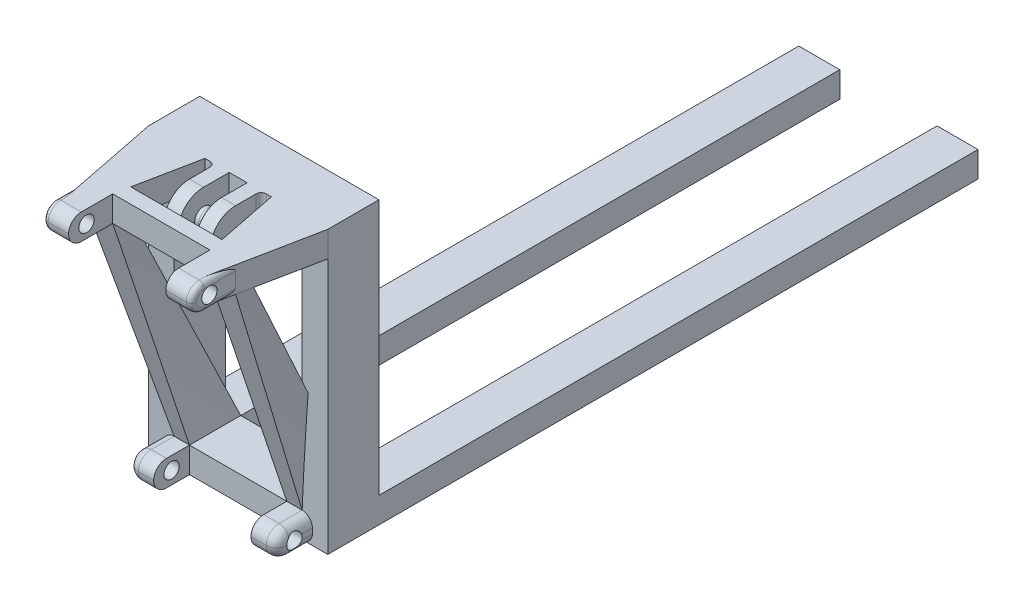
SolidWorks part; units mm, degrees
ref_plane "Front Plane" through (0, 0, 0) normal (0, 0, 1) x (1, 0, 0)
ref_plane "Top Plane" through (0, 0, 0) normal (0, 1, 0) x (1, 0, 0)
ref_plane "Right Plane" through (0, 0, 0) normal (1, 0, 0) x (0, 0, -1)
sketch "Sketch1" plane through (0, 0, 0) normal (0, 0, 1) x (1, 0, 0)
  line L1 (-17.5, -27.5) -> (17.5, -27.5)
  line L2 (-17.5, -27.5) -> (-17.5, 27.5)
  line L3 (-17.5, 27.5) -> (17.5, 27.5)
  line L4 (17.5, -27.5) -> (17.5, 27.5)
  line L5 (-17.5, -27.5) -> (17.5, 27.5) construction
  line L6 (-17.5, 27.5) -> (17.5, -27.5) construction
  point P0 (0, 0)
  dimension "D1" = 35
  dimension "D2" = 55
extrude "Boss-Extrude1" add sketch "Sketch1" along normal blind 3
sketch "Sketch2" plane through (0, 0, 3) normal (0, 0, 1) x (1, 0, 0)
  line L18 (-14.5, 27.5) -> (-9.5, 27.5)
  line L19 (-14.5, 27.5) -> (-14.5, 22.5)
  line L20 (-9.5, 27.5) -> (-9.5, 22.5)
  line L21 (-14.5, 22.5) -> (-9.5, 22.5)
  line L22 (17.5, 27.5) -> (-17.5, 27.5) construction
  line L23 (9.5, 27.5) -> (14.5, 27.5)
  line L24 (9.5, 27.5) -> (9.5, 22.5)
  line L25 (14.5, 27.5) -> (14.5, 22.5)
  line L26 (9.5, 22.5) -> (14.5, 22.5)
  line L27 (-9.5, -27.5) -> (-14.5, -27.5)
  line L28 (-9.5, -27.5) -> (-9.5, -22.5)
  line L29 (-14.5, -27.5) -> (-14.5, -22.5)
  line L30 (-9.5, -22.5) -> (-14.5, -22.5)
  line L31 (-17.5, -27.5) -> (17.5, -27.5) construction
  line L32 (9.5, -27.5) -> (14.5, -27.5)
  line L33 (9.5, -27.5) -> (9.5, -22.5)
  line L34 (14.5, -27.5) -> (14.5, -22.5)
  line L35 (9.5, -22.5) -> (14.5, -22.5)
  line L36 (-17.5, 27.5) -> (-17.5, -27.5) construction
  line L37 (17.5, -27.5) -> (17.5, 27.5) construction
  dimension "D1" = 5
  dimension "D2" = 3
  dimension "D3" = 3
  dimension "D4" = 3
  dimension "D5" = 3
  dimension "D6" = 5
extrude "Boss-Extrude2" add sketch "Sketch2" along normal blind 7
sketch "Sketch3" plane through (-14.5, 0, 0) normal (-1, 0, 0) x (0, 0, 1)
  line L0 (3, 27.5) -> (10, 22.5)
  line L1 (3, -22.5) -> (10, -27.5)
  circle A0 centre (6.5, 25) radius 1.5
  circle A1 centre (6.5, -25) radius 1.5
  dimension "D1" = 3
  dimension "D2" = 3
extrude "Cut-Extrude1" cut sketch "Sketch3" against normal up to surface (29 mm away) contours L1 A1 | L1 A1 region at (-14.5, -24.482, 6.87) region at (-14.5, -25.518, 6.13) up to face at (14.5, 25, 6.5)
fillet "Fillet1" radius 2.5 4 edges at (12, -27.5, 10) (12, -22.5, 10) (-12, -27.5, 10) (-12, -22.5, 10)
sketch "Sketch4" plane through (0, 0, 10) normal (0, 0, 1) x (1, 0, 0)
  line L1 (-9.5, 27.5) -> (-14.5, 27.5)
  line L2 (-9.5, 27.5) -> (-9.5, 22.5)
  line L3 (-9.5, 22.5) -> (-14.5, 22.5)
  line L4 (-14.5, 27.5) -> (-14.5, 22.5)
  line L5 (14.5, 27.5) -> (9.5, 27.5)
  line L6 (14.5, 27.5) -> (14.5, 22.5)
  line L7 (14.5, 22.5) -> (9.5, 22.5)
  line L8 (9.5, 27.5) -> (9.5, 22.5)
extrude "Boss-Extrude3" add sketch "Sketch4" along normal blind 16.6176
sketch "Sketch5" plane through (-14.5, 0, 0) normal (-1, 0, 0) x (0, 0, 1)
  line L0 (26.6176, 22.5) -> (3, 22.5) construction
  line L1 (26.6176, 27.5) -> (19.6176, 27.5)
  line L2 (26.6176, 27.5) -> (26.6176, 22.5)
  line L3 (26.6176, 22.5) -> (19.6176, 22.5)
  line L4 (19.6176, 27.5) -> (19.6176, 22.5)
  line L5 (19.6176, 27.5) -> (26.6176, 22.5)
  circle A0 centre (23.1176, 25) radius 1.5
  dimension "D2" = 3
  dimension "D1" = 7
extrude "Cut-Extrude2" cut sketch "Sketch5" against normal up to surface (29 mm away) contours L5 A0 | L5 A0 region at (-14.5, 25.518, 23.4877) region at (-14.5, 24.482, 22.7476) up to face at (14.5, 25, 14.8088)
fillet "Fillet2" radius 2.5 4 edges at (12, 22.5, 26.6176) (12, 27.5, 26.6176) (-12, 22.5, 26.6176) (-12, 27.5, 26.6176)
fillet "Fillet3" radius 2 8 edges at (-14.5, -27.5, 5.25) (-14.5, -26.7678, 9.2678) (-14.5, -22.5, 5.25) (14.5, -22.5, 5.25) (14.5, -27.5, 5.25) (14.5, -26.7678, 9.2678) (-14.5, -23.2322, 9.2678) (14.5, -23.2322, 9.2678)
chamfer "Chamfer1" distance 3 distance2 15 2 edges at (-14.5, 25, 3) (14.5, 25, 3) first distance on face at (0, -4.1667, 3)
fillet "Fillet5" radius 1 8 edges at (-14.5, 22.5, 21.0588) (-14.5, 23.2322, 25.8854) (-14.5, 27.5, 21.0588) (14.5, 27.5, 21.0588) (14.5, 22.5, 21.0588) (14.5, 23.2322, 25.8854) (-14.5, 26.7678, 25.8854) (14.5, 26.7678, 25.8854)
sketch "Sketch6" plane through (0, 0, 3) normal (0, 0, 1) x (1, 0, 0)
  line L0 (-4.5, 27.5) -> (4.5, 27.5)
  line L1 (9.5, 27.5) -> (-9.5, 27.5) construction
  line L3 (-4.5, 27.5) -> (-1.75, 27.5)
  line L4 (-4.5, 27.5) -> (-4.5, 17.5)
  line L5 (-4.5, 17.5) -> (-1.75, 17.5)
  line L6 (-1.75, 27.5) -> (-1.75, 17.5)
  line L7 (4.5, 27.5) -> (1.75, 27.5)
  line L8 (4.5, 27.5) -> (4.5, 17.5)
  line L9 (4.5, 17.5) -> (1.75, 17.5)
  line L10 (1.75, 27.5) -> (1.75, 17.5)
  point P5 (0, 27.5)
  line M28 (9.5, 27.5) -> (-9.5, 27.5)
  dimension "D1" = 9
  dimension "D2" = 2.75
  dimension "D3" = 10
extrude "Boss-Extrude4" add sketch "Sketch6" along normal blind 10 contours L6 L0 L4 L5 | L10 L9 L8 M28 region at (3.125, 22.5, 3) region at (-3.125, 22.5, 3)
sketch "Sketch7" plane through (-4.5, 0, 0) normal (-1, 0, 0) x (0, 0, 1)
  line L0 (3, 27.5) -> (13, 17.5)
  circle A0 centre (8, 22.5) radius 1.75
  dimension "D1" = 3.5
fillet "Fillet6" radius 5 4 edges at (-3.125, 17.5, 13) (3.125, 17.5, 13) (3.125, 27.5, 13) (-3.125, 27.5, 13)
fillet "Fillet7" radius 1 2 edges at (-4.5, 22.5, 3) (4.5, 22.5, 3)
extrude "Boss-Extrude5" add sketch "Sketch7" against normal blind 1.25 from surface contours L0 A0 | L0 A0 region at (-4.5, 23.0252, 8.5252) region at (-4.5, 21.9748, 7.4748) starting at face at (-1.75, 22.5, 7.4142)
sketch "Sketch9" plane through (4.5, 0, 0) normal (1, 0, 0) x (0, 0, -1)
  line L0 (-8, 17.5) -> (-8, 27.5)
  circle A0 centre (-8, 22.5) radius 1.75
  dimension "D1" = 3.5
extrude "Boss-Extrude6" add sketch "Sketch9" against normal blind 1.25 from surface contours L0 A0 | L0 A0 region at (4.5, 22.5, 8.7427) region at (4.5, 22.5, 7.2573) starting at face at (1.75, 22.5, 7.4142)
chamfer "Chamfer2" distance 3 distance2 15 2 edges at (9.5, 25, 3) (-9.5, 25, 3) first distance on face at (0, -1.0714, 3)
sketch "Sketch10" plane through (5.6731, 0, -1.1346) normal (-0.9806, 0, 0.1961) x (0.1961, 0, 0.9806)
  line L0 (19.5136, 22.5) -> (4.2165, 22.5) construction
  line L1 (19.5136, 27.5) -> (16.5136, 27.5)
  line L2 (19.5136, 27.5) -> (19.5136, 22.5)
  line L3 (19.5136, 22.5) -> (16.5136, 22.5)
  line L4 (16.5136, 27.5) -> (16.5136, 22.5)
  dimension "D1" = 3
extrude "Boss-Extrude7" add sketch "Sketch10" along direction (-1, 0, 0) on the side of the normal up to surface (19 mm away) up to face at (-8, 25, 10.5)
fillet "Fillet8" radius 0.5 2 edges at (0.5, 24.25, 8) (-0.5, 24.25, 8)
sketch "Sketch12" plane through (0, 22.5, 0) normal (0, -1, 0) x (1, 0, 0)
  line L0 (-9.5, 18) -> (-8.9117, 15.0583)
  line L1 (-8.9117, 15.0583) -> (-15.0883, 15.0583)
  line L2 (-13.5, 23) -> (-17.5, 3) construction
  line L3 (-15.0883, 15.0583) -> (-14.5, 18)
  line L4 (-14.5, 18) -> (-9.5, 18)
sketch "Sketch13" plane through (0, 22.5, 0) normal (0, -1, 0) x (1, 0, 0)
  line L0 (9.5, 18) -> (8.9117, 15.0583)
  line L1 (8.9117, 15.0583) -> (15.0883, 15.0583)
  line L2 (17.5, 3) -> (13.5, 23) construction
  line L3 (15.0883, 15.0583) -> (14.5, 18)
  line L4 (14.5, 18) -> (9.5, 18)
sketch "Sketch15" plane through (0, 0, 0) normal (0, 0, -1) x (-1, 0, 0)
  line L1 (-17.5, 27.5) -> (17.5, 27.5)
  line L2 (-17.5, 27.5) -> (-17.5, -27.5)
  line L3 (-17.5, -27.5) -> (17.5, -27.5)
  line L4 (17.5, 27.5) -> (17.5, -27.5)
extrude "Boss-Extrude8" add sketch "Sketch15" along normal blind 7
sketch "Sketch16" plane through (0, 0, 3) normal (0, 0, 1) x (1, 0, 0)
  line L0 (-17.5, 22.5) -> (-17.5, -27.5) construction
  line L1 (-17.5, -22.5) -> (17.5, -22.5)
  line L2 (-17.5, -22.5) -> (-17.5, 17.5)
  line L3 (-17.5, 17.5) -> (17.5, 17.5)
  line L4 (17.5, -22.5) -> (17.5, 17.5)
  line L5 (17.5, -27.5) -> (17.5, 22.5) construction
  line L6 (5.5, 17.5) -> (1.75, 17.5) construction
  line L7 (-9.5, -22.5) -> (-12.5, -22.5) construction
  line L8 (5.5, 17.5) -> (17.5, 22.5)
  line L9 (17.5, 22.5) -> (17.5, 17.5)
  line L10 (-5.5, 17.5) -> (-17.5, 22.5)
  line L11 (-17.5, 22.5) -> (-17.5, 17.5)
  line M9 (5.5, 17.5) -> (1.75, 17.5)
  line M13 (-1.75, 17.5) -> (-5.5, 17.5)
  line M18 (-17.5, 22.5) -> (-17.5, -27.5)
  line M23 (-12.5, -22.5) -> (-9.5, -22.5)
  line M27 (9.5, -22.5) -> (12.5, -22.5)
  line M32 (17.5, -27.5) -> (17.5, 22.5)
extrude "Cut-Extrude5" cut sketch "Sketch16" against normal up to surface (10 mm away) contours L3 L10 M18 | L8 L3 M32 | L3 L1 M18 M23 M27 M32 M9 M13 region at (0, -2.5, 3) region at (-13.5, 19.1667, 3) region at (13.5, 19.1667, 3) up to face at (0, 0, -7)
sketch "Sketch17" plane through (0, -22.5, 0) normal (0, 1, 0) x (1, 0, 0)
  line L0 (-17.5, 7) -> (17.5, 7) construction
  line L1 (12.5, -3) -> (9.5, -3)
  line L2 (12.5, -3) -> (12.5, 7)
  line L3 (12.5, 7) -> (9.5, 7)
  line L4 (9.5, -3) -> (9.5, 7)
sketch "Sketch18" plane through (0, -22.5, 0) normal (0, 1, 0) x (1, 0, 0)
  line L0 (-17.5, 7) -> (17.5, 7) construction
  line L1 (-12.5, -3) -> (-9.5, -3)
  line L2 (-12.5, -3) -> (-12.5, 7)
  line L3 (-12.5, 7) -> (-9.5, 7)
  line L4 (-9.5, -3) -> (-9.5, 7)
loft "Loft3" add profiles "Sketch13", "Sketch17" connector at (15.0883, 22.5, 15.0583) connector at (12.5, -22.5, -7)
loft "Loft4" add profiles "Sketch12", "Sketch18" connector at (-8.9117, 22.5, 15.0583) connector at (-9.5, -22.5, -7)
sketch "Sketch19" plane through (0, -22.5, 0) normal (0, 1, 0) x (1, 0, 0)
  line L1 (17.5, -3) -> (12.5, -3)
  line L2 (17.5, -3) -> (17.5, 7)
  line L3 (17.5, 7) -> (12.5, 7)
  line L4 (12.5, -3) -> (12.5, 7)
  line L5 (-17.5, -3) -> (-12.5, -3)
  line L6 (-17.5, -3) -> (-17.5, 7)
  line L7 (-17.5, 7) -> (-12.5, 7)
  line L8 (-12.5, -3) -> (-12.5, 7)
extrude "Boss-Extrude9" add sketch "Sketch19" along normal up to surface (50 mm away) up to face at (0, 27.5, 6.2645)
sketch "Sketch21" plane through (0, 0, -7) normal (0, 0, -1) x (-1, 0, 0)
  line L0 (-17.5, 27.5) -> (-17.5, -27.5) construction
  line L1 (-17.5, -27.5) -> (-9.5, -27.5)
  line L2 (-17.5, -27.5) -> (-17.5, -22.5)
  line L3 (-17.5, -22.5) -> (-9.5, -22.5)
  line L4 (-9.5, -27.5) -> (-9.5, -22.5)
  line L5 (-17.5, -27.5) -> (17.5, -27.5) construction
  line L8 (-8.9117, 22.5) -> (-9.5, -22.5) construction
  line L9 (-12.5, -22.5) -> (-9.5, -22.5) construction
  line L10 (9.5, -22.5) -> (8.9117, 22.5) construction
  line L11 (9.5, -22.5) -> (17.5, -22.5)
  line L12 (9.5, -22.5) -> (9.5, -27.5)
  line L13 (9.5, -27.5) -> (17.5, -27.5)
  line L14 (17.5, -22.5) -> (17.5, -27.5)
  line L15 (9.5, -22.5) -> (12.5, -22.5) construction
  point P10 (0, 0)
extrude "Boss-Extrude10" add sketch "Sketch21" along normal blind 117
